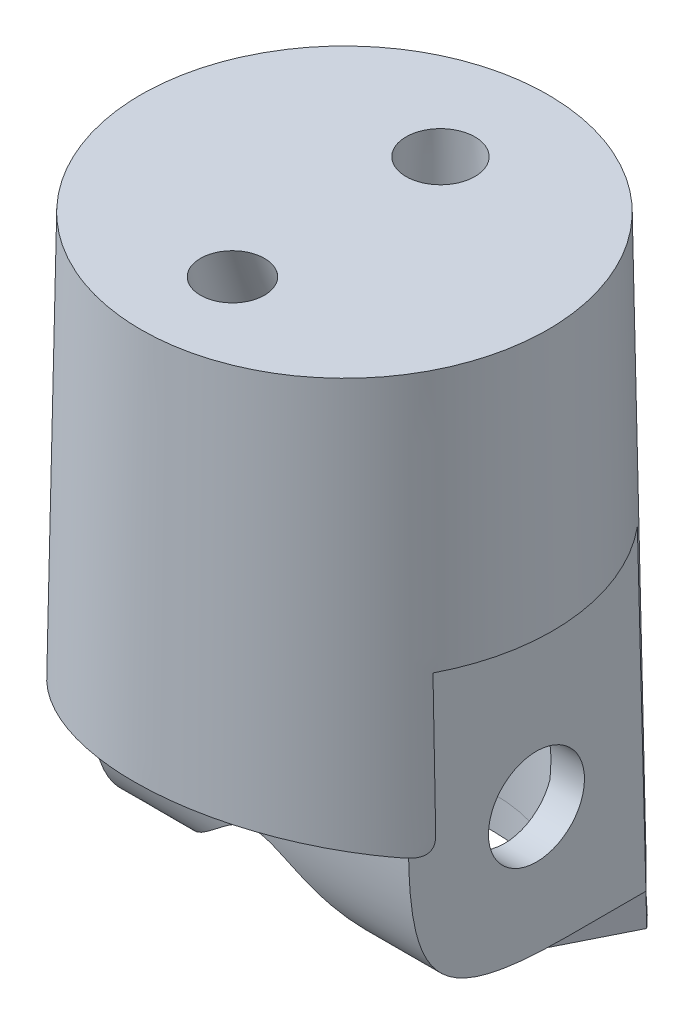
SolidWorks part; units mm, degrees
material "ABS"
ref_plane "Front Plane" through (0, 0, 0) normal (0, 0, 1) x (1, 0, 0)
ref_plane "Top Plane" through (0, 0, 0) normal (0, 1, 0) x (1, 0, 0)
ref_plane "Right Plane" through (0, 0, 0) normal (1, 0, 0) x (0, 0, -1)
sketch "Sketch1" plane through (0, 0, 0) normal (0, 1, 0) x (1, 0, 0)
  circle A0 centre (0, 0) radius 6.5
  dimension "D1" = 13
extrude "Boss-Extrude1" add sketch "Sketch1" along normal blind 18 draft 1 and the other way blind 10 draft 1
ref_plane "Plane1" through (0, 0, 3) normal (0, 0, 1) x (1, 0, 0)
sketch "Sketch2" plane through (0, 0, 3) normal (0, 0, 1) x (1, 0, 0)
  line L0 (-6.6746, -10) -> (6.6746, -10) construction
  line L1 (5, 0) -> (-5, 0)
  line L2 (5, 0) -> (5, -10)
  line L3 (5, -10) -> (-5, -10)
  line L4 (-5, 0) -> (-5, -10)
  line L5 (5, 0) -> (-5, -10) construction
  line L6 (5, -10) -> (-5, 0) construction
  line L8 (10.5451, 0) -> (-10.5451, 0)
  line L9 (10.5451, 0) -> (10.5451, -10)
  line L10 (10.5451, -10) -> (-10.5451, -10)
  line L11 (-10.5451, 0) -> (-10.5451, -10)
  line L12 (10.5451, 0) -> (-10.5451, -10) construction
  line L13 (10.5451, -10) -> (-10.5451, 0) construction
  point P0 (0, -5)
  point P9 (0, -5)
  dimension "D1" = 10
  dimension "D2" = 10
extrude "Cut-Extrude1" cut sketch "Sketch2" against normal through all contours L8 L11 L10 L4 | L10 L9 L8 L2
sketch "Sketch3" plane through (5, 0, 0) normal (1, 0, 0) x (0, 0, -1)
  line L0 (-3, -10) -> (-3, -5)
  line L1 (-3, -5) -> (-18.9219, -0.7337)
  line L2 (-18.9219, -0.7337) -> (-18.9219, -10)
  line L3 (-18.9219, -10) -> (-3, -10)
  dimension "D1" = 5
  dimension "D2" = 105
extrude "Cut-Extrude2" cut sketch "Sketch3" against normal through all both and the other way through all
sketch "Sketch4" plane through (5, 0, 0) normal (1, 0, 0) x (0, 0, -1)
  line L0 (4.4215, -10) -> (-3, -10) construction
  line L1 (-3, -5) -> (-3, -10) construction
  circle A0 centre (1, -6) radius 1.5
  dimension "D1" = 4
  dimension "D2" = 3
  dimension "D3" = 4
extrude "Cut-Extrude3" cut sketch "Sketch4" against normal through all both and the other way through all contours A0
fillet "Fillet1" radius 5 1 edges at (0, -10, 3)
fillet "Fillet2" radius 5 1 edges at (0, 18, 6.1858)
sketch "Sketch5" plane through (0, 0, 0) normal (1, 0, 0) x (0, 0, -1)
  line L0 (-6.3588, 8.0873) -> (6.3588, 8.0873) construction
  line L1 (-8.3203, 8.0873) -> (10.1495, 8.0873)
  line L2 (-8.3203, 8.0873) -> (-8.3203, 20.7829)
  line L3 (-8.3203, 20.7829) -> (10.1495, 20.7829)
  line L4 (10.1495, 8.0873) -> (10.1495, 20.7829)
extrude "Cut-Extrude4" cut sketch "Sketch5" against normal through all both and the other way through all
sketch "Sketch6" plane through (0, -10, 0) normal (0, -1, 0) x (1, 0, 0)
  line L0 (-4, -2.419) -> (-4, 0.581)
  line L1 (4, -2.419) -> (4, 0.581)
  line L2 (-5, 3) -> (-5, -2) construction
  line L3 (5, -2) -> (5, 3) construction
  line L4 (-4, -0.919) -> (4, -0.919) construction
  arc A1 (-4, 0.581) -> (4, 0.581) centre (0, -1.8379) cw
  arc A2 (-3.5018, -3.0966) -> (3.5018, -3.0966) centre (0, 0) ccw
  arc A3 (-4, -2.419) -> (4, -2.419) centre (0, 0) ccw
  dimension "D2" = 1
  dimension "D3" = 1
  dimension "D4" = 1.5
  dimension "D1" = 2
extrude "Cut-Extrude5" cut sketch "Sketch6" against normal blind 10
sketch "Sketch7" plane through (0, 8.0873, 0) normal (0, 1, 0) x (1, 0, 0)
  circle A1 centre (0, 1.1) radius 3.5
  dimension "D1" = 7
  dimension "D2" = 1.1
extrude "Cut-Extrude6" [suppressed] cut sketch "Sketch7" against normal up to next contours A1
sketch "Sketch8" [suppressed] plane through (0, 8.0873, 0) normal (0, 1, 0) x (1, 0, 0)
  line L0 (3.5, 1.1) -> (-3.5, 1.1) construction
  line L1 (-3.2692, 2.35) -> (3.2692, 2.35)
  line L2 (-3.2692, -0.15) -> (3.2692, -0.15)
  circle A0 centre (0, 1.1) radius 3.5 construction
  arc A1 (-3.2692, 2.35) -> (-3.2692, -0.15) centre (0, 1.1) ccw
  arc A2 (3.2692, -0.15) -> (3.2692, 2.35) centre (0, 1.1) ccw
  point P6 (0, 1.1)
  circle M4 centre (0, 1.1) radius 3.5
  dimension "D1" = 2.5
extrude "Boss-Extrude2" [suppressed] add sketch "Sketch8" against normal blind 2 contours L0 L1 A1 M4 | A1 L0 L2 M4
fillet "Fillet3" radius 0.5 2 edges
sketch "Sketch9" plane through (0, -10, 0) normal (0, -1, 0) x (1, 0, 0)
  line L0 (-4, -2.419) -> (-5, -4.4215)
  line L1 (4, -2.419) -> (5, -4.4215)
  line L6 (5, -2) -> (4, -2)
  line L7 (4, -2) -> (4, -2.419)
  line L8 (-4, -2.419) -> (-4, -2)
  line L9 (-4, -2) -> (-5, -2)
  line L10 (-5, -2) -> (-5, -4.4215)
  line L11 (5, -4.4215) -> (5, -2)
  arc A2 (-4, -2.419) -> (4, -2.419) centre (0, 0) ccw
  arc A3 (-5, -4.4215) -> (5, -4.4215) centre (0, 0) ccw
  arc A4 (-4, -2.419) -> (4, -2.419) centre (0, 0) ccw
  arc A5 (-5, -4.4215) -> (5, -4.4215) centre (0, 0) ccw
  dimension "D1" = 0
extrude "Boss-Extrude3" add sketch "Sketch9" along normal blind 1 draft 1 draft outward yes
sketch "Sketch11" plane through (0, 0, 0) normal (0, -1, 0) x (1, 0, 0)
  circle A0 centre (0, -3) radius 1.5
  point P2 (0, 0)
  dimension "D1" = 3
  dimension "D2" = 3
extrude "Cut-Extrude7" cut sketch "Sketch11" against normal through all draft 3
sketch "Sketch12" plane through (0, 0, 0) normal (0, -1, 0) x (1, 0, 0)
  circle A0 centre (0, 1) radius 1.5
  dimension "D1" = 3
  dimension "D2" = 1
sketch "Sketch13" plane through (0, 8.0873, 0) normal (0, 1, 0) x (1, 0, 0)
  circle A0 centre (0, -3.5) radius 1
  point P2 (0, 0)
  dimension "D1" = 2
  dimension "D2" = 3.5
loft "Cut-Loft1" cut profiles "Sketch12", "Sketch13"
